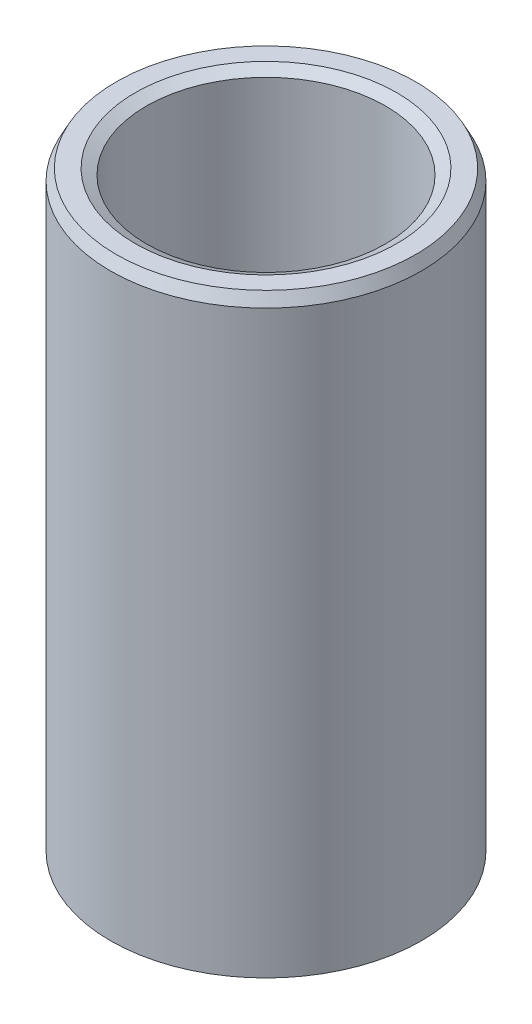
SolidWorks part; units mm, degrees
ref_plane "Front Plane" through (0, 0, 0) normal (0, 0, 1) x (1, 0, 0)
ref_plane "Top Plane" through (0, 0, 0) normal (0, 1, 0) x (1, 0, 0)
ref_plane "Right Plane" through (0, 0, 0) normal (1, 0, 0) x (0, 0, -1)
sketch "Sketch1" plane through (0, 0, 0) normal (0, 1, 0) x (1, 0, 0)
  circle A0 centre (0, 0) radius 25
  dimension "SLEEVE_OD" = 50
extrude "Boss-Extrude1" add sketch "Sketch1" along normal blind 95.9867
sketch "Sketch2" plane through (0, 0, 0) normal (0, 1, 0) x (1, 0, 0)
  circle A0 centre (0, 0) radius 19.212
  dimension "BORE_D" = 38.424
extrude "Cut-Extrude1" cut sketch "Sketch2" along normal through all
chamfer "Chamfer1" distance 1.8092 angle 27.522 4 edges at (0, 95.9867, 19.212) (0, 0, 19.212) (0, 0, 25) (0, 95.9867, 25) first distance on face at (0, 95.9867, 19.212) first distance on face at (0, 0, 19.212) first distance on face at (0, 95.9867, 25)
